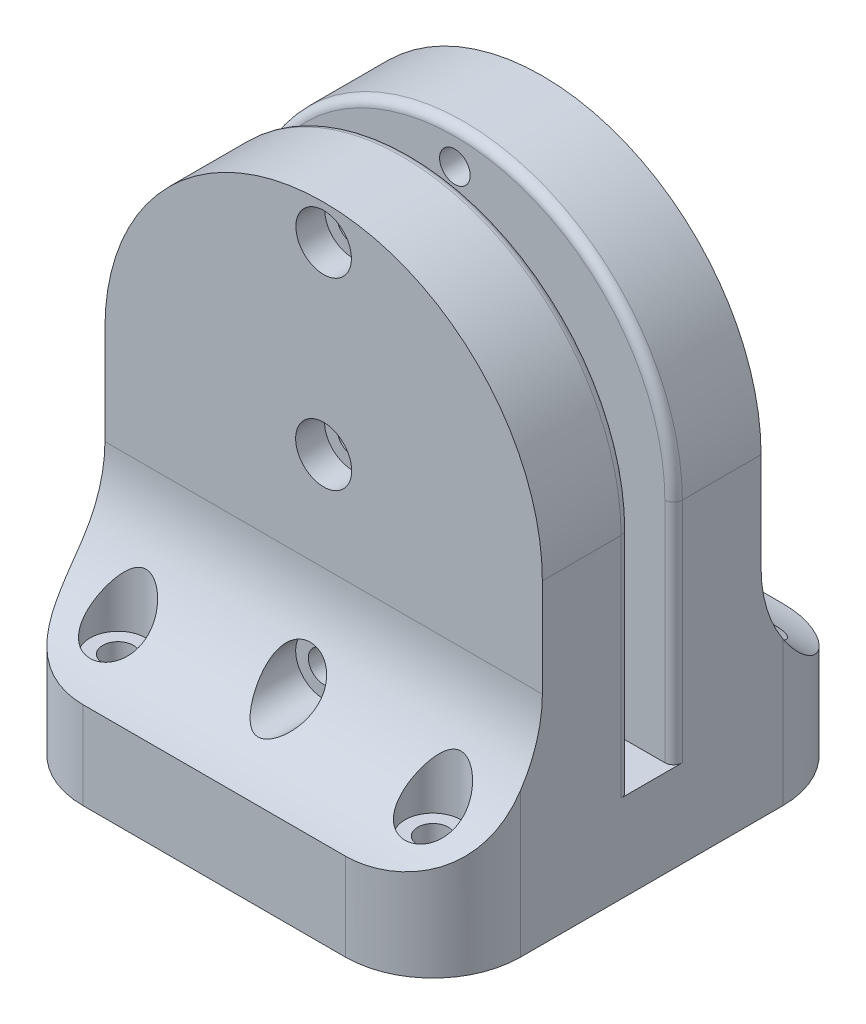
SolidWorks part; units mm, degrees
ref_plane "正面" through (0, 0, 0) normal (0, 0, 1) x (1, 0, 0)
ref_plane "平面" through (0, 0, 0) normal (0, 1, 0) x (1, 0, 0)
ref_plane "右側面" through (0, 0, 0) normal (1, 0, 0) x (0, 0, -1)
sketch "ｽｹｯﾁ1" plane through (0, 0, 0) normal (0, 1, 0) x (1, 0, 0)
  line L1 (25, 25) -> (-25, 25)
  line L2 (25, 25) -> (25, -25)
  line L3 (25, -25) -> (-25, -25)
  line L4 (-25, 25) -> (-25, -25)
  line L5 (25, 25) -> (-25, -25) construction
  line L6 (25, -25) -> (-25, 25) construction
  point P0 (0, 0)
  dimension "D1" = 50
  dimension "D2" = 50
extrude "ﾎﾞｽ - 押し出し1" add sketch "ｽｹｯﾁ1" along normal blind 10
sketch "ｽｹｯﾁ2" plane through (0, 0, 0) normal (0, 0, 1) x (1, 0, 0)
  line L0 (25, 10) -> (-25, 10)
  line L1 (-25, 10) -> (25, 10)
  line L4 (-25, 36) -> (-25, 10)
  line L5 (-25, 10) -> (25, 10)
  line L6 (-12, 10) -> (6.5, 10)
  line L7 (-25, 10) -> (25, 10)
  line L8 (25, 36) -> (25, 10)
  arc A1 (25, 36) -> (-25, 36) centre (0, 36) ccw
  circle A2 centre (0, 36) radius 1.75
  dimension "D1" = 26
  dimension "D3" = 0
  dimension "D2" = 25
  dimension "D6" = 3.5
  dimension "D4" = 26
  dimension "D5" = 26
sketch "ｽｹｯﾁ6" plane through (0, 0, 0) normal (0, 1, 0) x (1, 0, 0)
  line L0 (0, -25) -> (0, 25) construction
  line L1 (-25, -25) -> (25, -25) construction
  line L2 (25, 25) -> (-25, 25) construction
  line L3 (-25, 0) -> (25, 0) construction
  line L4 (-25, 25) -> (-25, -25) construction
  line L5 (25, -25) -> (25, 25) construction
  circle A0 centre (-18, -18) radius 1.75
  circle A1 centre (18, -18) radius 1.75
  circle A2 centre (18, 18) radius 1.75
  circle A3 centre (-18, 18) radius 1.75
  dimension "D1" = 3.5
  dimension "D2" = 18
  dimension "D3" = 18
extrude "ｶｯﾄ - 押し出し3" cut sketch "ｽｹｯﾁ6" against normal blind 5 and the other way through all
fillet "ﾌｨﾚｯﾄ1" radius 10 4 edges at (-25, 5, 25) (-25, 5, -25) (25, 5, -25) (25, 5, 25)
extrude "ﾎﾞｽ - 押し出し5" add sketch "ｽｹｯﾁ2" along normal blind 10 from offset 2.5 contours L8 A1 L4 L0 L5 A2 region at (0, 33.1466, 0)
extrude "ﾎﾞｽ - 押し出し6" add sketch "ｽｹｯﾁ2<12>" against normal blind 10 from offset 2.5 contours L8 A1 L4 L0 L5 A2 region at (0, 33.1466, 0) offset against normal yes
sketch "ｽｹｯﾁ2<12>" plane through (0, 0, 0) normal (0, 0, 1) x (1, 0, 0) same geometry as "ｽｹｯﾁ2"
sketch "ｽｹｯﾁ13" plane through (0, 0, 0) normal (0, 0, 1) x (1, 0, 0)
  circle A0 centre (0, 36) radius 21
  circle A1 centre (0, 15) radius 1.75
  circle A2 centre (0, 57) radius 1.75
  point P10 (0, 36)
  dimension "D1" = 42
  dimension "D2" = 3.5
  dimension "D3" = 2
extrude "ｶｯﾄ - 押し出し4" cut sketch "ｽｹｯﾁ13" against normal through all both and the other way through all contours A1 | A2
sketch "ｽｹｯﾁ14" plane through (0, 10, 0) normal (0, 1, 0) x (1, 0, 0)
  line L0 (0, 25) -> (0, -25) construction
  line L1 (15, 25) -> (-15, 25) construction
  line L2 (-15, -25) -> (15, -25) construction
  line L3 (-25, 0) -> (25, 0) construction
  line L4 (-25, 2.5) -> (-25, -2.5) construction
  line L5 (25, -2.5) -> (25, 2.5) construction
  circle A0 centre (18, 18) radius 3.2
  circle A1 centre (18, -18) radius 3.2
  circle A2 centre (-18, -18) radius 3.2
  circle A3 centre (-18, 18) radius 3.2
  dimension "D1" = 6.4
fillet "ﾌｨﾚｯﾄ3" radius 15 2 edges at (0, 10, -12.5)
extrude "ｶｯﾄ - 押し出し6" cut sketch "ｽｹｯﾁ14" along normal through all
sketch "ｽｹｯﾁ15" plane through (0, 0, 0) normal (0, 0, 1) x (1, 0, 0)
  circle A0 centre (0, 15) radius 3.2
  dimension "D1" = 6.4
extrude "ｶｯﾄ - 押し出し7" cut sketch "ｽｹｯﾁ15" along normal through all from offset 12.5
extrude "ｶｯﾄ - 押し出し8" cut sketch "ｽｹｯﾁ15<2>" against normal through all from offset 12.5 offset against normal yes
sketch "ｽｹｯﾁ15<2>" plane through (0, 0, 0) normal (0, 0, 1) x (1, 0, 0) same geometry as "ｽｹｯﾁ15"
sketch "ｽｹｯﾁ16" plane through (0, 0, 0) normal (0, 0, 1) x (1, 0, 0)
  circle A0 centre (0, 36) radius 3.2
  circle A1 centre (0, 57) radius 3.175
  dimension "D1" = 6.4
  dimension "D2" = 6.35
extrude "ｶｯﾄ - 押し出し9" cut sketch "ｽｹｯﾁ16" against normal blind 3.3 from offset 12.5
extrude "ｶｯﾄ - 押し出し10" cut sketch "ｽｹｯﾁ16<2>" along normal blind 3.3 from offset 12.5 offset against normal yes
sketch "ｽｹｯﾁ16<2>" plane through (0, 0, 0) normal (0, 0, 1) x (1, 0, 0) same geometry as "ｽｹｯﾁ16"
fillet "ﾌｨﾚｯﾄ5" radius 1 6 edges at (25, 23, -2.5) (-25, 23, -2.5) (0, 61, -2.5) (0, 61, 2.5)
